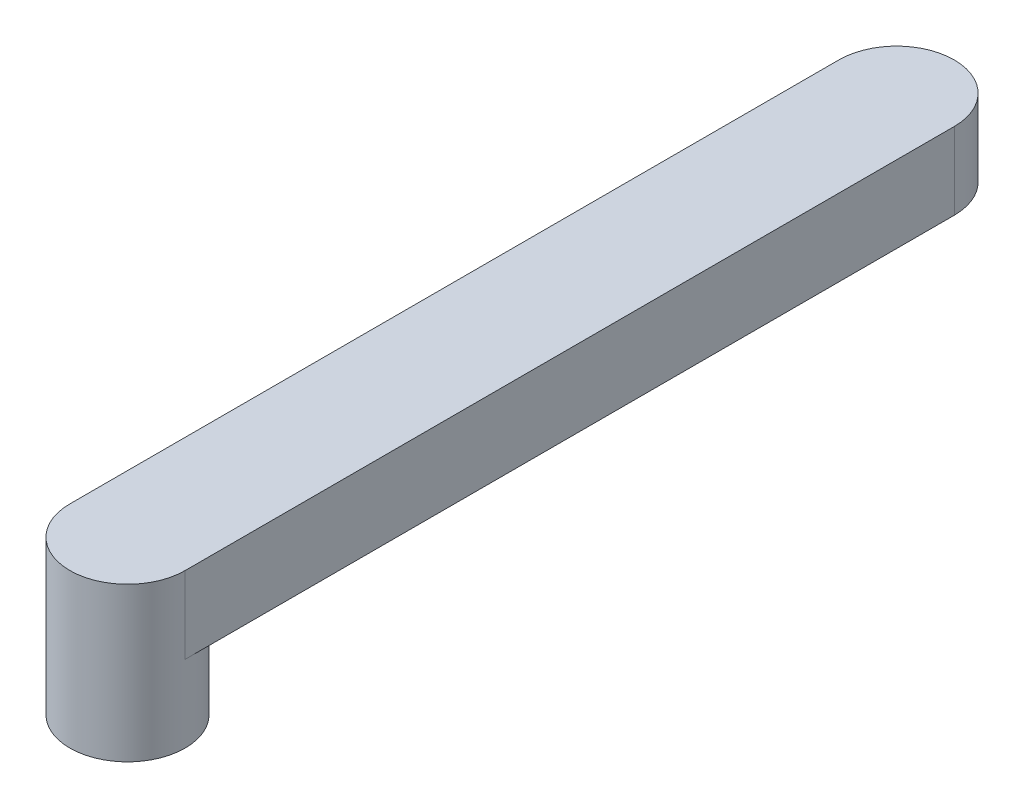
SolidWorks part; units mm, degrees
ref_plane "Front Plane" through (0, 0, 0) normal (0, 0, 1) x (1, 0, 0)
ref_plane "Top Plane" through (0, 0, 0) normal (0, 1, 0) x (1, 0, 0)
ref_plane "Right Plane" through (0, 0, 0) normal (1, 0, 0) x (0, 0, -1)
sketch "Sketch1" plane through (0, 0, 0) normal (0, 1, 0) x (1, 0, 0)
  line L0 (0, 0) -> (0, -15.24) construction
  line L1 (3.175, 0) -> (3.175, -15.24)
  line L2 (-3.175, 0) -> (-3.175, -15.24)
  line L3 (0, -15.24) -> (0, 10.16) construction
  line L4 (-1.905, -15.24) -> (-1.905, 10.16)
  line L5 (1.905, -15.24) -> (1.905, 10.16)
  arc A0 (3.175, 0) -> (-3.175, 0) centre (0, 0) ccw
  arc A1 (-3.175, -15.24) -> (3.175, -15.24) centre (0, -15.24) ccw
  arc A2 (-1.905, -15.24) -> (1.905, -15.24) centre (0, -15.24) ccw
  arc A3 (1.905, 10.16) -> (-1.905, 10.16) centre (0, 10.16) ccw
  circle A4 centre (0, -15.24) radius 1.905
  point P3 (0, -7.62)
  point P10 (0, -2.54)
  dimension "D1" = 15.24
  dimension "D2" = 6.35
  dimension "D3" = 25.4
  dimension "D4" = 3.81
extrude "Boss-Extrude1" add sketch "Sketch1" along normal blind 2.54 contours L5 A3 L4 A0 | A4 L5 A0 L4 region at (0, 0, -7.3228) region at (0, 0, 5.39)
extrude "Boss-Extrude2" add sketch "Sketch1<3>" along normal mid plane 5.08 contours A2 A4 region at (0, 0, 15.24)
sketch "Sketch1<3>" plane through (0, 0, 0) normal (0, 1, 0) x (1, 0, 0) same geometry as "Sketch1"
